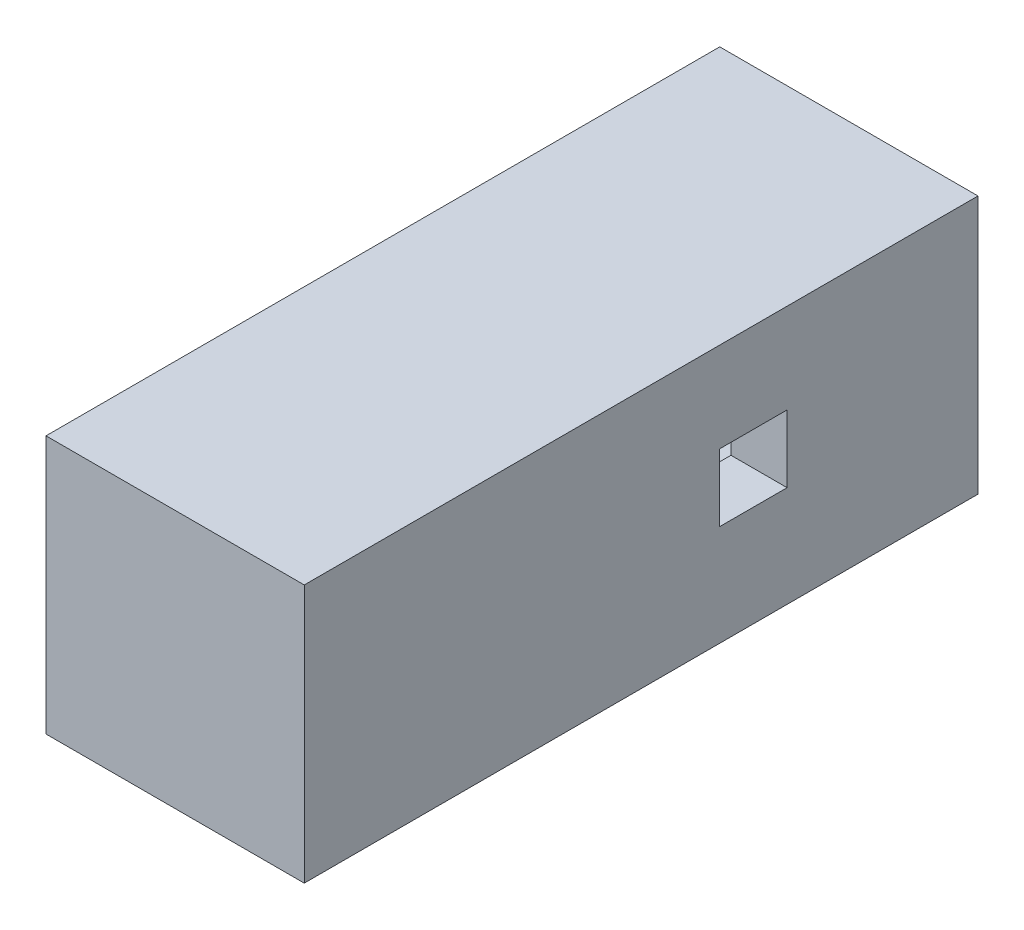
SolidWorks part; units mm, degrees
ref_plane "前视基准面" through (0, 0, 0) normal (0, 0, 1) x (1, 0, 0)
ref_plane "上视基准面" through (0, 0, 0) normal (0, 1, 0) x (1, 0, 0)
ref_plane "右视基准面" through (0, 0, 0) normal (1, 0, 0) x (0, 0, -1)
sketch "草图3" plane through (0, 0, 0) normal (0, 0, 1) x (1, 0, 0)
  line L1 (0, 0) -> (-23, 0)
  line L2 (0, 0) -> (0, 23)
  line L3 (0, 23) -> (-23, 23)
  line L4 (-23, 0) -> (-23, 23)
  line L5 (-5, 5) -> (-18, 5)
  line L6 (-5, 5) -> (-5, 18)
  line L7 (-5, 18) -> (-18, 18)
  line L8 (-18, 5) -> (-18, 18)
  dimension "D1" = 23
  dimension "D2" = 23
  dimension "D3" = 13
  dimension "D4" = 13
extrude "凸台-拉伸1" add sketch "草图3" along normal blind 33
sketch "草图6" plane through (0, 0, 33) normal (0, 0, 1) x (1, 0, 0)
  line L4 (0, 0) -> (0, 23)
  line L5 (0, 23) -> (-23, 23)
  line L6 (-23, 23) -> (-23, 0)
  line L7 (-23, 0) -> (0, 0)
  line L8 (0, 0) -> (0, 23)
  line L9 (0, 23) -> (-23, 23)
  line L10 (-23, 23) -> (-23, 0)
  line L11 (-23, 0) -> (0, 0)
  dimension "D1" = 0
extrude "凸台-拉伸3" add sketch "草图6" along normal blind 27
sketch "草图9" plane through (0, 0, 0) normal (1, 0, 0) x (0, 0, -1)
  line L1 (-23, 15) -> (-17, 15)
  line L2 (-23, 15) -> (-23, 9)
  line L3 (-23, 9) -> (-17, 9)
  line L4 (-17, 15) -> (-17, 9)
  dimension "D1" = 6
  dimension "D2" = 6
extrude "凸台-拉伸5" add sketch "草图9" against normal blind 5
extrude "切除-拉伸3" cut sketch "草图9<2>" against normal blind 5
sketch "草图9<2>" plane through (0, 0, 0) normal (1, 0, 0) x (0, 0, -1) same geometry as "草图9"
sketch "草图10" plane through (-23, 0, 0) normal (-1, 0, 0) x (0, 0, 1)
  line L0 (23, 9) -> (17, 9) construction
  line L1 (17, 15) -> (23, 15) construction
  line L2 (19, 15) -> (21, 15)
  line L3 (19, 15) -> (19, 9)
  line L4 (19, 9) -> (21, 9)
  line L5 (21, 15) -> (21, 9)
extrude "切除-拉伸4" cut sketch "草图10" against normal blind 5
